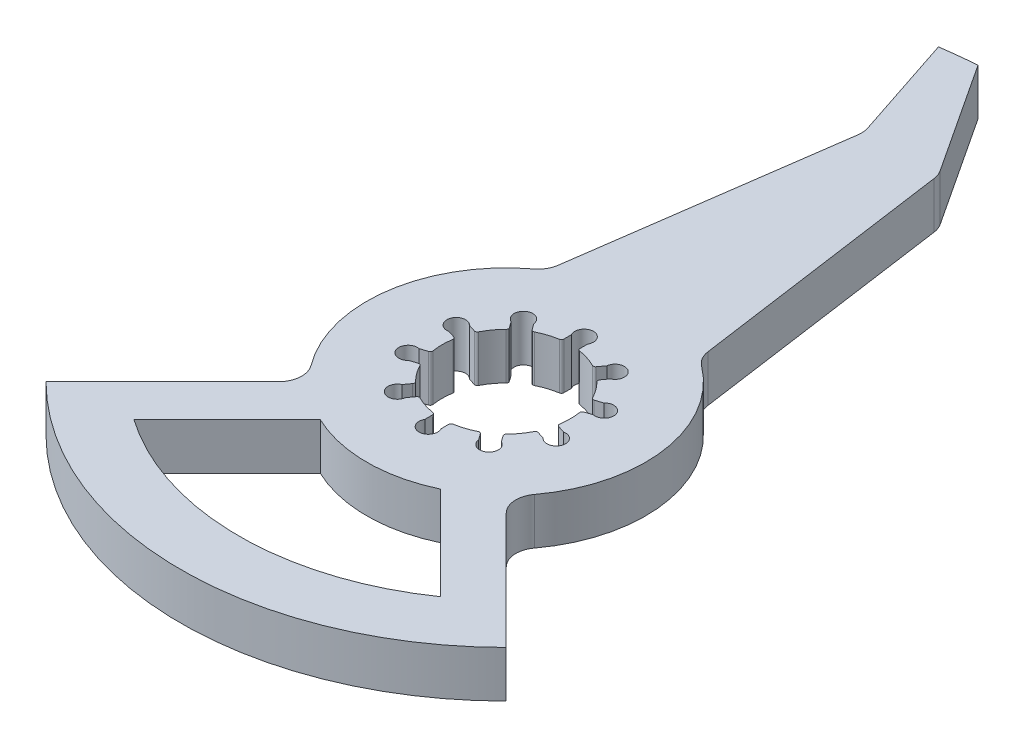
SolidWorks part; units mm, degrees
material "AISI Type A2 Tool Steel"
ref_plane "Front Plane" through (0, 0, 0) normal (0, 0, 1) x (1, 0, 0)
ref_plane "Top Plane" through (0, 0, 0) normal (0, 1, 0) x (1, 0, 0)
ref_plane "Right Plane" through (0, 0, 0) normal (1, 0, 0) x (0, 0, -1)
other "Center of Mass"
other "Bounding Box"
ref_plane "Default Plane" through (0, 2.286, 19.05) normal (0, -1, 0) x (-1, 0, 0)
sketch "Sketch1" plane through (0, 0, 0) normal (0, 1, 0) x (1, 0, 0)
  circle A0 centre (0, 0) radius 139.7 construction
  circle A1 centre (0, 0) radius 38.1
  circle A2 centre (0, 0) radius 17.4625
  dimension "D1" = 279.4
  dimension "D2" = 76.2
  dimension "D3" = 34.925
extrude "Boss-Extrude1" add sketch "Sketch1" along normal mid plane 12.7
sketch "Sketch2" plane through (0, 6.35, 0) normal (0, 1, 0) x (1, 0, 0)
  line L0 (-10.16, 107.95) -> (-20.8497, 31.8889)
  line L1 (20.8497, 31.8889) -> (10.16, 107.95)
  line L2 (10.16, 107.95) -> (-10.4431, 139.3091)
  line L3 (-10.16, 107.95) -> (-20.1788, 138.235)
  line L4 (0, 0) -> (0, 139.7) construction
  line L5 (-10.16, 107.95) -> (0, 107.95) construction
  line L6 (0, 107.95) -> (10.16, 107.95) construction
  line L7 (-20.1788, 138.235) -> (0, 0) construction
  circle A0 centre (0, 0) radius 139.7 construction
  circle A1 centre (0, 0) radius 139.7 construction
  arc A2 (-20.1788, 138.235) -> (-10.4431, 139.3091) centre (0, 0) cw
  circle A5 centre (0, 0) radius 38.1
  arc A6 (20.8497, 31.8889) -> (-20.8497, 31.8889) centre (0, 0) ccw
  arc A7 (-20.8497, 31.8889) -> (20.8497, 31.8889) centre (0, 0) ccw construction
  point P5 (10.0532, 139.6587)
  point P6 (7.936, 139.7)
  point P7 (-10.16, 113.6763)
  point P10 (0, 139.7)
  point P13 (5.4377, 139.7)
  point P16 (-11.8113, 139.7)
  dimension "D3" = 10
  dimension "D4" = 31.75
  dimension "D5" = 8
  dimension "D6" = 10.16
  dimension "D1" = 15
  dimension "D2" = 0
extrude "Boss-Extrude2" add sketch "Sketch2" against normal through all
sketch "Sketch3" plane through (0, 6.35, 0) normal (0, 1, 0) x (1, 0, 0)
  line L0 (-62.8618, -62.8618) -> (-26.9408, -26.9408)
  line L1 (26.9408, -26.9408) -> (62.8618, -62.8618)
  line L2 (0, -38.1) -> (0, -88.9) construction
  line L4 (-26.9408, -26.9408) -> (0, 0) construction
  line L5 (0, 0) -> (26.9408, -26.9408) construction
  arc A0 (-62.8618, -62.8618) -> (62.8618, -62.8618) centre (0, 0) ccw
  circle A1 centre (0, 0) radius 38.1 construction
  arc A3 (-26.9408, -26.9408) -> (26.9408, -26.9408) centre (0, 0) ccw
  point P9 (0, -80.908)
  point P13 (0, -88.9)
  dimension "D2" = 88.9
  dimension "D1" = 90
extrude "Boss-Extrude3" add sketch "Sketch3" against normal through all
sketch "Sketch5" plane through (0, 6.35, 0) normal (0, 1, 0) x (1, 0, 0)
  line L0 (0, 17.4625) -> (0, 21.2725) construction
  line L2 (-2.2225, 17.3205) -> (2.2225, 17.3205)
  line L3 (-2.2225, 17.3205) -> (-2.2225, 20.0168)
  line L5 (2.2225, 17.3205) -> (2.2225, 20.0168)
  arc A0 (2.2225, 20.0168) -> (-2.2225, 20.0168) centre (0, 21.2725) ccw
  circle A1 centre (0, 0) radius 17.4625 construction
  circle A2 centre (0, 21.2725) radius 4.5847 construction
  dimension "D2" = 5.1054
  dimension "D4" = 9.1694
  dimension "D1" = 3.81
  dimension "D3" = 4.445
extrude "Cut-Extrude2" cut sketch "Sketch5" against normal through all
pattern_circular "CirPattern1" count 10 over 360 about axis through (0, 6.35, 0) along (0, -1, 0) of "Cut-Extrude2"
sketch "Sketch6" plane through (0, 6.35, 0) normal (0, 1, 0) x (1, 0, 0)
  circle A0 centre (0, 0) radius 17.526
  arc A1 (-11.9788, 12.7062) -> (-15.786, 7.466) centre (0, 0) ccw construction
  dimension "D1" = 0.0635
extrude "Cut-Extrude3" cut sketch "Sketch6" against normal through all
fillet "Fillet1" radius 6.35 6 edges at (-26.9408, 0, 26.9408) (26.9408, 0, 26.9408) (20.8497, 0, -31.8889) (10.16, 0, -107.95) (-20.8497, 0, -31.8889) (-10.16, 0, -107.95)
fillet "Fillet6" radius 0.635 20 edges at (-12.0164, 0, -12.758) (-15.8469, 0, -7.4858) (-17.2204, 0, -3.2584) (-17.2204, 0, 3.2584) (-15.8469, 0, 7.4858) (-12.0164, 0, 12.758) (-8.4203, 0, 15.3707) (-2.2225, 0, 17.3845) (2.2225, 0, 17.3845) (8.4203, 0, 15.3707) (12.0164, 0, 12.758) (15.8469, 0, 7.4858) (17.2204, 0, 3.2584) (17.2204, 0, -3.2584) (15.8469, 0, -7.4858) (12.0164, 0, -12.758) (8.4203, 0, -15.3707) (2.2225, 0, -17.3845) (-2.2225, 0, -17.3845) (-8.4203, 0, -15.3707)
sketch "Sketch7" plane through (0, 6.35, 0) normal (0, 1, 0) x (1, 0, 0)
  line L0 (-41.8693, -59.8298) -> (-16.4197, -34.3803)
  line L1 (16.4197, -34.3803) -> (41.8693, -59.8298)
  line L3 (-31.1085, -31.1085) -> (-62.8618, -62.8618) construction
  line L4 (62.8618, -62.8618) -> (31.1085, -31.1085) construction
  line L5 (-41.8693, -59.8298) -> (-50.8496, -50.8496) construction
  line L6 (41.8693, -59.8298) -> (50.8496, -50.8496) construction
  arc A0 (-16.4197, -34.3803) -> (16.4197, -34.3803) centre (0, 0) ccw
  arc A1 (-41.8693, -59.8298) -> (41.8693, -59.8298) centre (0, 0) ccw
  arc A2 (-62.8618, -62.8618) -> (62.8618, -62.8618) centre (0, 0) ccw construction
  arc A3 (30.5131, -22.8158) -> (22.933, 30.4251) centre (0, 0) ccw construction
  dimension "D1" = 15.875
  dimension "D2" = 12.7
extrude "Cut-Extrude4" cut sketch "Sketch7" against normal through all
equation "\"Unit Measure\"= \"BoundingVolume\" / \"Thickness\"'in^2"
